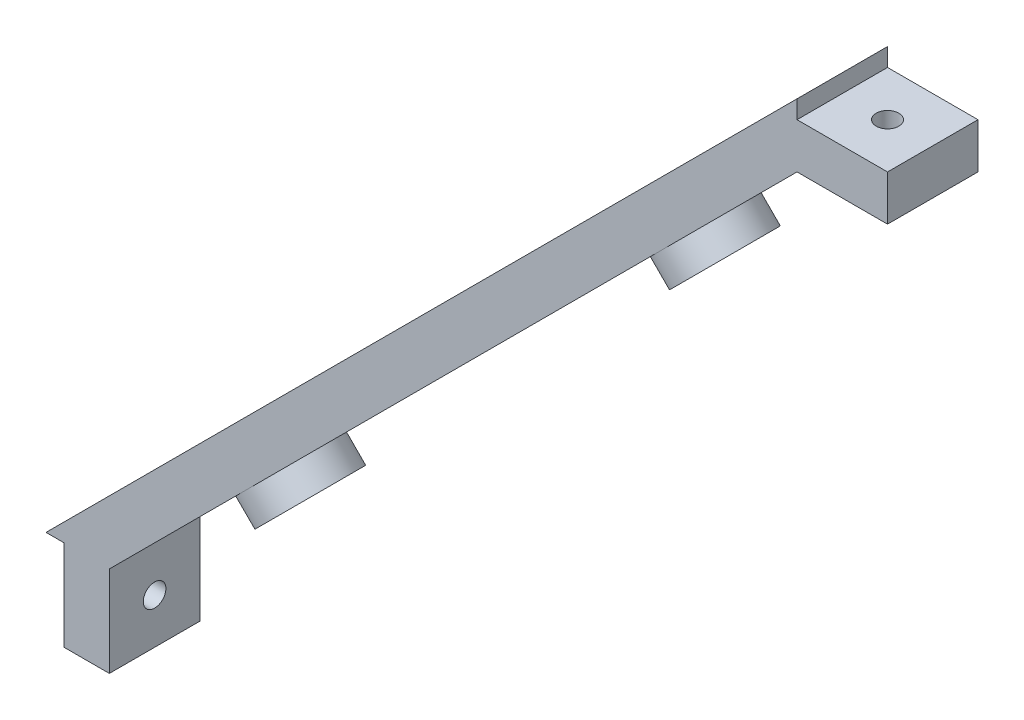
SolidWorks part; units mm, degrees
ref_plane "Front Plane" through (0, 0, 0) normal (0, 0, 1) x (1, 0, 0)
ref_plane "Top Plane" through (0, 0, 0) normal (0, 1, 0) x (1, 0, 0)
ref_plane "Right Plane" through (0, 0, 0) normal (1, 0, 0) x (0, 0, -1)
sketch "Sketch1" plane through (0, 0, 0) normal (0, 0, 1) x (1, 0, 0)
  line L0 (-41.5, -41.5) -> (41.5, 41.5)
  line L1 (41.5, 41.5) -> (41.5, 39.5)
  line L2 (-39.5, -41.5) -> (-39.5, -51.5)
  line L3 (-39.5, -51.5) -> (-34.5, -51.5)
  line L4 (41.5, 39.5) -> (51.5, 39.5)
  line L5 (-34.5, -51.5) -> (-34.5, -41.5)
  line L6 (-41.5, -41.5) -> (-39.5, -41.5)
  line L7 (-34.5, -41.5) -> (41.5, 34.5)
  line L8 (41.5, 34.5) -> (51.5, 34.5)
  line L9 (51.5, 39.5) -> (51.5, 34.5)
  point P13 (0, 0)
  dimension "D6" = 81
  dimension "D1" = 45
  dimension "D2" = 10
  dimension "D3" = 5
  dimension "D4" = 81
  dimension "D5" = 117.3797
  dimension "D7" = 2
extrude "Main" add sketch "Sketch1" along normal mid plane 10
sketch "Sketch2" plane through (41.5, 0, 0) normal (1, 0, 0) x (0, 0, -1)
  line L0 (5, -41.5) -> (-5, -51.5) construction
  line L1 (-5, -41.5) -> (5, -51.5) construction
  circle A0 centre (0, -46.5) radius 1.25
  dimension "D1" = 2.5
extrude "FixHole1" cut sketch "Sketch2" against normal through all
sketch "Sketch3" plane through (0, -41.5, 0) normal (0, -1, 0) x (-1, 0, 0)
  line L4 (-41.5, 5) -> (-51.5, -5) construction
  line L5 (-41.5, -5) -> (-51.5, 5) construction
  circle A1 centre (-46.5, 0) radius 1.25
  dimension "D1" = 2.5
extrude "FixHole2" cut sketch "Sketch3" against normal through all
sketch "Sketch6" plane through (3.5, -3.5, 0) normal (-0.7071, 0.7071, 0) x (0, 0, 1)
  circle A0 centre (0, 40) radius 1.25
  dimension "D1" = 2.5
  dimension "D2" = 40
extrude "Cut-Extrude2" cut sketch "Sketch6" along normal through all
pattern_linear "LPattern1" count 5 spacing 20 along (-0.7071, -0.7071, 0) of "Cut-Extrude2"
sketch "Sketch7" plane through (3.5, -3.5, 0) normal (-0.7071, 0.7071, 0) x (0, 0, 1)
  line L0 (-5, 58.6899) -> (-5, -58.6899) construction
  circle A0 centre (0, -32.4) radius 5
  circle A1 centre (0, 32.4) radius 5
  dimension "D1" = 10
  dimension "D2" = 64.8
  dimension "D3" = 32.4
  dimension "D4" = 5
extrude "Boss-Extrude1" add sketch "Sketch7" against normal blind 3
sketch "Sketch8" plane through (5.6213, -5.6213, 0) normal (0.7071, -0.7071, 0) x (0, 0, -1)
  circle A0 centre (0, 32.4) radius 1.25
  circle A1 centre (0, 32.4) radius 5 construction
  circle A2 centre (0, -32.4) radius 1.25
  circle A4 centre (0, -32.4) radius 5 construction
  dimension "D1" = 2.5
extrude "Cut-Extrude3" cut sketch "Sketch8" against normal through all
